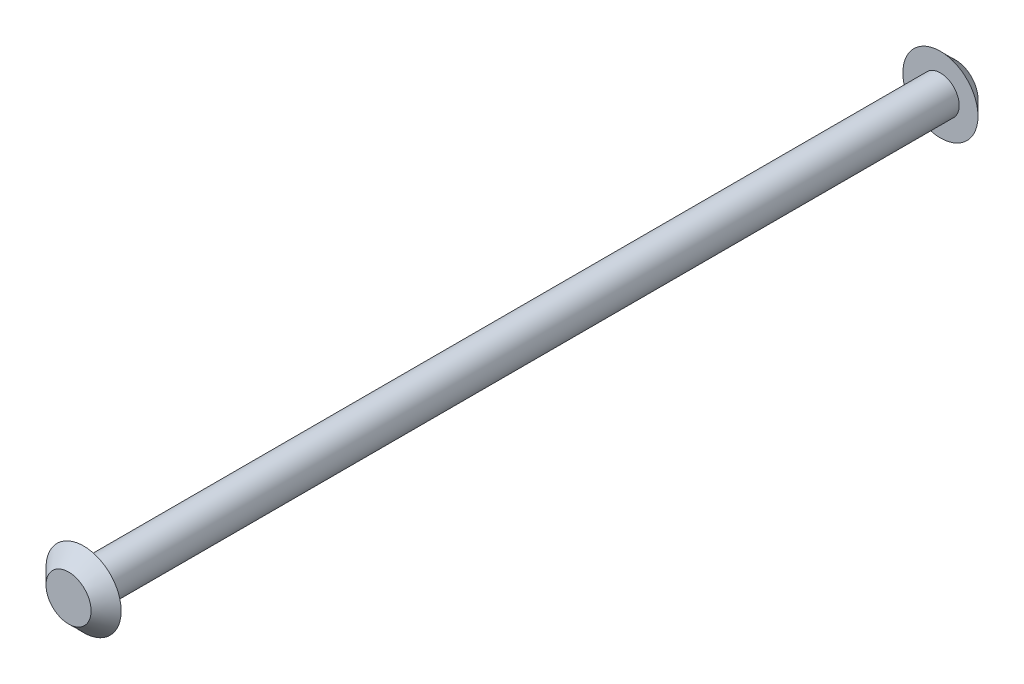
SolidWorks part; units mm, degrees
ref_plane "Front Plane" through (0, 0, 0) normal (0, 0, 1) x (1, 0, 0)
ref_plane "Top Plane" through (0, 0, 0) normal (0, 1, 0) x (1, 0, 0)
ref_plane "Right Plane" through (0, 0, 0) normal (1, 0, 0) x (0, 0, -1)
sketch "Sketch1" plane through (0, 0, 0) normal (0, 0, 1) x (1, 0, 0)
  circle A0 centre (0, 0) radius 3.175
  dimension "D1" = 6.35
extrude "Boss-Extrude1" add sketch "Sketch1" along normal blind 144.78
sketch "Sketch2" plane through (0, 0, 144.78) normal (0, 0, 1) x (1, 0, 0)
  circle A0 centre (0, 0) radius 6.35
  dimension "D1" = 12.7
extrude "Boss-Extrude2" add sketch "Sketch2" along normal blind 2.54
chamfer "Chamfer1" distance 2.54 angle 45 1 edges at (6.35, 0, 147.32)
ref_plane "Plane1" through (0, 0, 72.39) normal (0, 0, -1) x (-1, 0, 0)
mirror "Mirror1" about plane through (0, 0, 72.39) normal (0, 0, -1) of "Chamfer1", "Boss-Extrude2"
